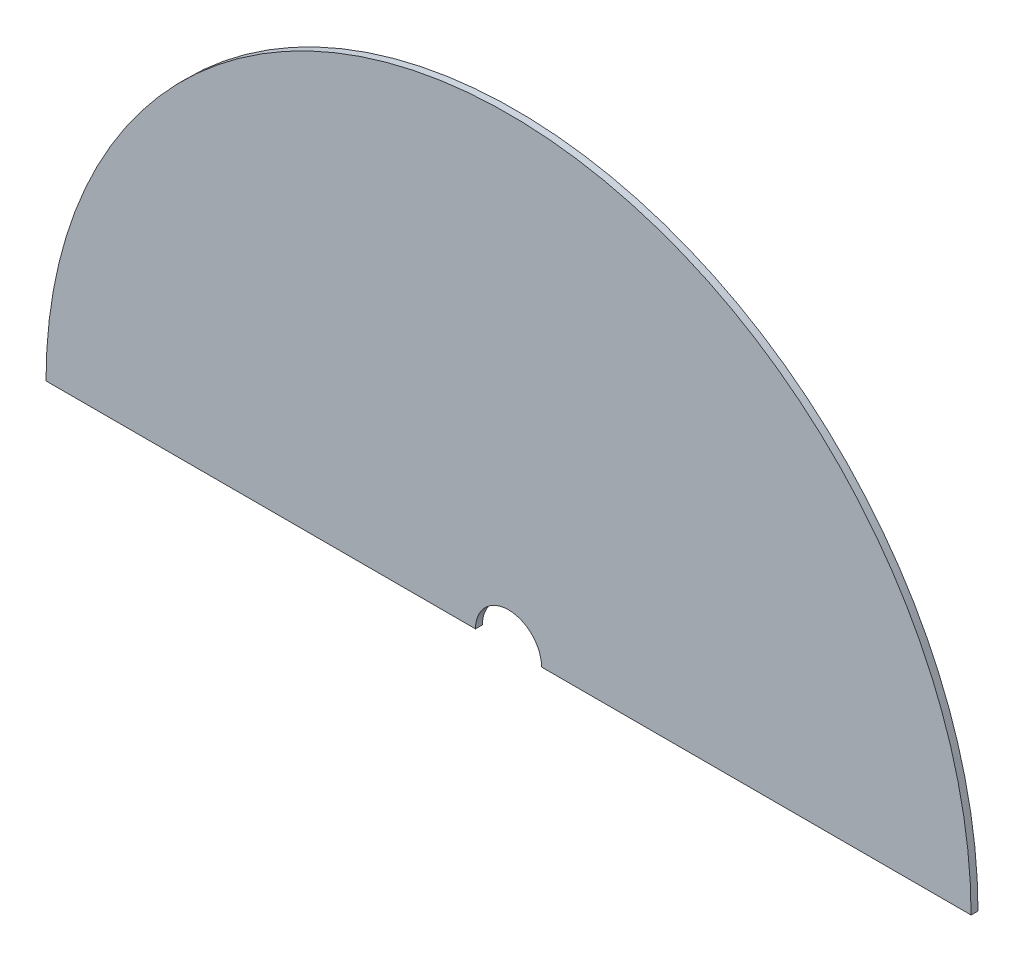
SolidWorks part; units mm, degrees
ref_plane "Front Plane" through (0, 0, 0) normal (0, 0, 1) x (1, 0, 0)
ref_plane "Top Plane" through (0, 0, 0) normal (0, 1, 0) x (1, 0, 0)
ref_plane "Right Plane" through (0, 0, 0) normal (1, 0, 0) x (0, 0, -1)
sketch "Sketch1" plane through (0, 0, 0) normal (0, 0, 1) x (1, 0, 0)
  line L0 (-177.8, 0) -> (-12.7, 0)
  line L1 (0, 0) -> (0, 177.8) construction
  line L17 (-12.7, 0) -> (0, 0) construction
  line L18 (12.7, 0) -> (177.8, 0)
  line L19 (-12.7, 0) -> (0, 0) construction
  line L20 (0, 0) -> (12.7, 0) construction
  arc A0 (-177.8, 0) -> (0, 177.8) centre (0, 0) cw
  arc A1 (0, 177.8) -> (177.8, 0) centre (0, 0) cw
  arc A2 (-12.7, 0) -> (12.7, 0) centre (0, 0) cw
  point P4 (15.0875, 0)
  point P5 (175.3053, 0)
  point P7 (0, 0)
  point P9 (0, 177.7775)
  point P10 (-175.3646, 0)
  point P11 (67.7613, 0)
  point P12 (41.5499, 0)
  point P13 (62.128, 0)
  point P14 (-50.8, 170.3884)
  point P15 (-50.8, 170.3884)
  point P17 (0, 0)
  point P18 (-14.3797, 0)
  point P19 (0, 0)
  point P20 (0, 0)
  point P21 (0, 168.1195)
  point P23 (0, 0)
  dimension "D2" = 177.8
  dimension "D9" = 12.7
base flange "Base-Flange1" sketch "Sketch1" thickness 2.6568 reverse thickness direction no parameters "D1"=0.7366
sketch "Bend-Lines1" [suppressed] plane through (0, 0, 0) normal (0, 1, 0) x (1, 0, 0)
sketch "Bounding-Box1" [suppressed] plane through (0, 0, 0) normal (0, 1, 0) x (1, 0, 0)
sheet metal parameters "Sheet-Metal1" thickness 2.6568 parameters "D1"=0.7366
flat pattern "Flat-Pattern1" [suppressed]
sketch "Bend-Lines2" plane through (0, 0, 0) normal (0, 0, 1) x (1, 0, 0)
  point P0 (-177.8, -1.6219)
  point P1 (177.8, -1.6219)
  point P2 (-101.6, -1.6219)
  point P3 (101.6, -1.6219)
sketch3d "Bounding-Box2" [suppressed]
  line L0 (-177.8, 0, 0) -> (177.8, 0, 0) construction
  line L1 (-177.8, 177.8, 0) -> (177.8, 177.8, 0) construction
  line L2 (-177.8, 0, 0) -> (-177.8, 177.8, 0) construction
  line L3 (177.8, 0, 0) -> (177.8, 177.8, 0) construction
